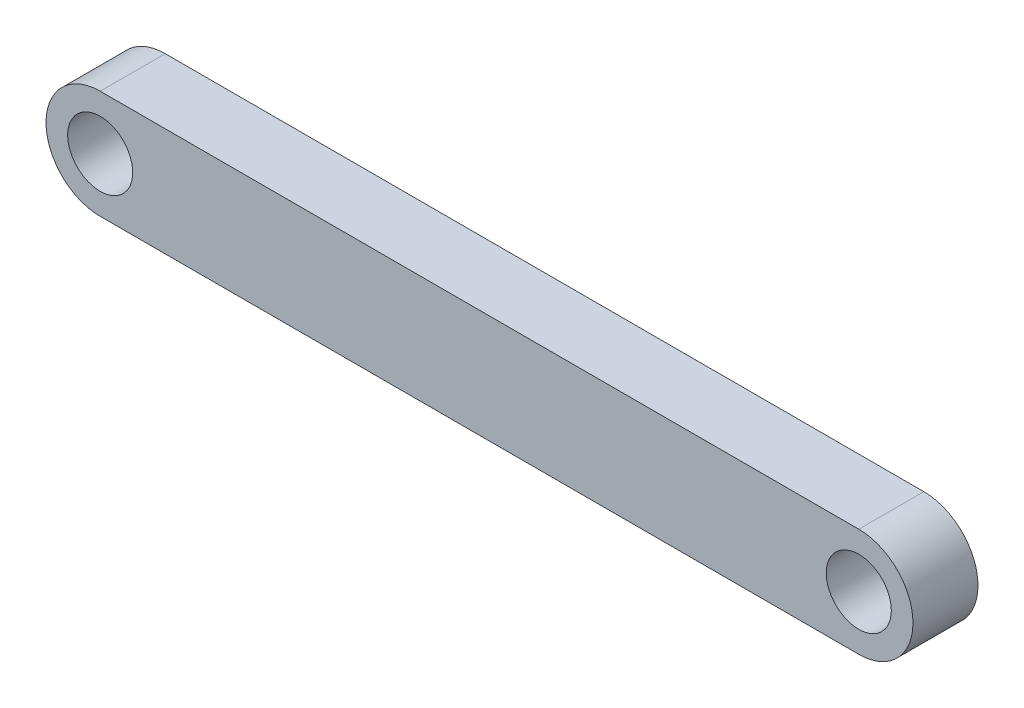
SolidWorks part; units mm, degrees
ref_plane "Ebene vorne" through (0, 0, 0) normal (0, 0, 1) x (1, 0, 0)
ref_plane "Ebene oben" through (0, 0, 0) normal (0, 1, 0) x (1, 0, 0)
ref_plane "Ebene rechts" through (0, 0, 0) normal (1, 0, 0) x (0, 0, -1)
sketch "Skizze1" plane through (0, 0, 0) normal (0, 0, 1) x (1, 0, 0)
  circle A0 centre (0, 680) radius 3.25
  circle A1 centre (70, 680) radius 3.25
sketch "Skizze2" plane through (0, 0, 0) normal (0, 0, 1) x (1, 0, 0)
  line L0 (0, 685) -> (70, 685)
  line L1 (0, 675) -> (70, 675)
  arc A0 (0, 685) -> (0, 675) centre (0, 680) ccw
  arc A1 (70, 675) -> (70, 685) centre (70, 680) ccw
  circle A2 centre (0, 680) radius 3
  circle A3 centre (70, 680) radius 3
  dimension "D1" = 10
extrude "Aufsatz-Linear austragen1" add sketch "Skizze2" along normal blind 3 and the other way blind 3
